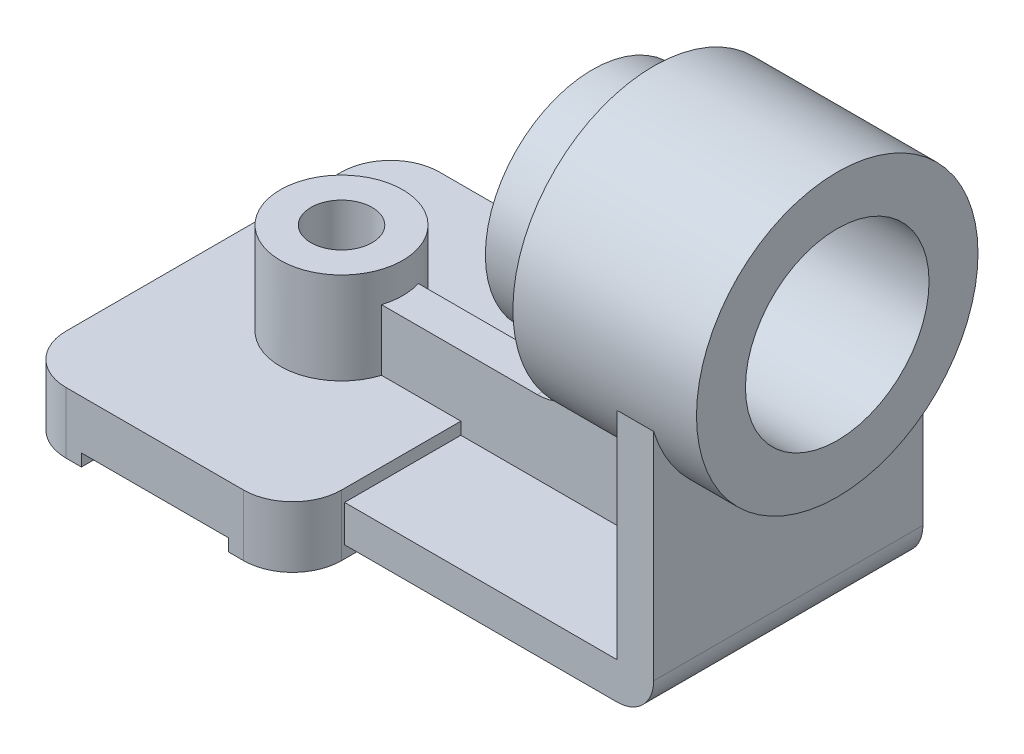
SolidWorks part; units mm, degrees
ref_plane "前视基准面" through (0, 0, 0) normal (0, 0, 1) x (1, 0, 0)
ref_plane "上视基准面" through (0, 0, 0) normal (0, 1, 0) x (1, 0, 0)
ref_plane "右视基准面" through (0, 0, 0) normal (1, 0, 0) x (0, 0, -1)
other "Configuration Table"
sketch "草图1" plane through (0, 0, 0) normal (0, 1, 0) x (1, 0, 0)
  line L1 (-14.5, 30.5) -> (14.5, 30.5)
  line L2 (-22.5, 22.5) -> (-22.5, -22.5)
  line L3 (-14.5, -30.5) -> (14.5, -30.5)
  line L4 (22.5, 22.5) -> (22.5, -22.5)
  line L5 (-22.5, 30.5) -> (22.5, -30.5) construction
  line L6 (-22.5, -30.5) -> (22.5, 30.5) construction
  arc A0 (14.5, 30.5) -> (22.5, 22.5) centre (14.5, 22.5) cw
  arc A1 (-22.5, -22.5) -> (-14.5, -30.5) centre (-14.5, -22.5) ccw
  arc A2 (-14.5, 30.5) -> (-22.5, 22.5) centre (-14.5, 22.5) ccw
  arc A3 (14.5, -30.5) -> (22.5, -22.5) centre (14.5, -22.5) ccw
  point P0 (0, 0)
  dimension "D3" = 8
  dimension "D1" = 61
  dimension "D2" = 45
extrude "凸台-拉伸1" add sketch "草图1" against normal blind 10
sketch "草图2" plane through (0, 0, 0) normal (0, 1, 0) x (1, 0, 0)
  circle A0 centre (0, 0) radius 10
  dimension "D1" = 20
extrude "凸台-拉伸2" add sketch "草图2" along normal blind 15
sketch "草图3" plane through (0, 0, 30.5) normal (0, 0, 1) x (1, 0, 0)
  line L0 (-14.5, -10) -> (14.5, -10) construction
  line L1 (-12, -8) -> (12, -8)
  line L2 (-12, -8) -> (-12, -12)
  line L3 (-12, -12) -> (12, -12)
  line L4 (12, -8) -> (12, -12)
  line L5 (-12, -8) -> (12, -12) construction
  line L6 (-12, -12) -> (12, -8) construction
  point P0 (0, -10)
  dimension "D1" = 24
  dimension "D2" = 4
extrude "切除-拉伸1" cut sketch "草图3" against normal up to surface (61 mm away) up to face at (0, -5, -30.5)
sketch "草图4" plane through (0, 15, 0) normal (0, 1, 0) x (1, 0, 0)
  circle A0 centre (0, 0) radius 5
  dimension "D1" = 10
extrude "切除-拉伸2" cut sketch "草图4" against normal up to surface (23 mm away) up to face at (0, -8, 0)
sketch "草图6" plane through (0, 0, 0) normal (0, 0, 1) x (1, 0, 0)
  line L0 (22.5, -10) -> (22.5, 0) construction
  line L1 (22.5, -2) -> (67, -2)
  line L2 (22.5, -2) -> (22.5, -8)
  line L3 (22.5, -8) -> (67, -8)
  line L5 (14.5, -10) -> (22.5, -10) construction
  line L6 (67, -2) -> (67, 40)
  line L7 (67, 40) -> (73, 40)
  line L8 (73, 40) -> (73, -2)
  line L9 (22.5, -2) -> (6.5, -2)
  line L10 (6.5, -2) -> (6.5, 10)
  line L11 (6.5, 10) -> (35, 10)
  line L12 (43, 18) -> (43, 40)
  line L13 (43, 40) -> (67, 40)
  line L14 (10, 15) -> (-10, 15) construction
  arc A0 (67, -8) -> (73, -2) centre (67, -2) ccw
  arc A1 (35, 10) -> (43, 18) centre (35, 18) ccw
  point P15 (6.5, 4)
  dimension "D4" = 6
  dimension "D8" = 8
  dimension "D1" = 2
  dimension "D2" = 6
  dimension "D3" = 44.5
  dimension "D5" = 42
  dimension "D6" = 16
  dimension "D7" = 5
  dimension "D9" = 30
extrude "凸台-拉伸3" add sketch "草图6" along normal mid plane 44 contours L3 A0 L8 L7 L6 L1 L2 region at (44.75, -2.6967, 0)
extrude "凸台-拉伸4" add sketch "草图6<3>" along normal mid plane 6 contours A1 L11 L10 L9 L1 L6 L13 L12 region at (45.7936, 14.4313, 0)
sketch "草图6<3>" plane through (0, 0, 0) normal (0, 0, 1) x (1, 0, 0) same geometry as "草图6"
sketch "草图7" plane through (73, 0, 0) normal (1, 0, 0) x (0, 0, -1)
  line L0 (-22, 40) -> (22, 40) construction
  circle A0 centre (0, 40) radius 23
  dimension "D1" = 46
extrude "凸台-拉伸5" add sketch "草图7" against normal blind 30 from offset 8
sketch "草图9" plane through (51, 0, 0) normal (-1, 0, 0) x (0, 0, 1)
  line L0 (3, 40) -> (-3, 40) construction
  circle A0 centre (0, 40) radius 17.5
  dimension "D1" = 35
extrude "凸台-拉伸6" add sketch "草图9" along normal blind 10
sketch "草图10" plane through (41, 0, 0) normal (-1, 0, 0) x (0, 0, 1)
  circle A0 centre (0, 40) radius 10
  dimension "D1" = 20
extrude "切除-拉伸3" cut sketch "草图10" against normal blind 15
sketch "草图12" plane through (56, 0, 0) normal (-1, 0, 0) x (0, 0, 1)
  circle A0 centre (0, 40) radius 17
  dimension "D1" = 34
extrude "切除-拉伸4" cut sketch "草图12" against normal blind 3
sketch "草图13" plane through (59, 0, 0) normal (-1, 0, 0) x (0, 0, 1)
  circle A0 centre (0, 40) radius 15
  dimension "D1" = 30
extrude "切除-拉伸5" cut sketch "草图13" against normal blind 22
